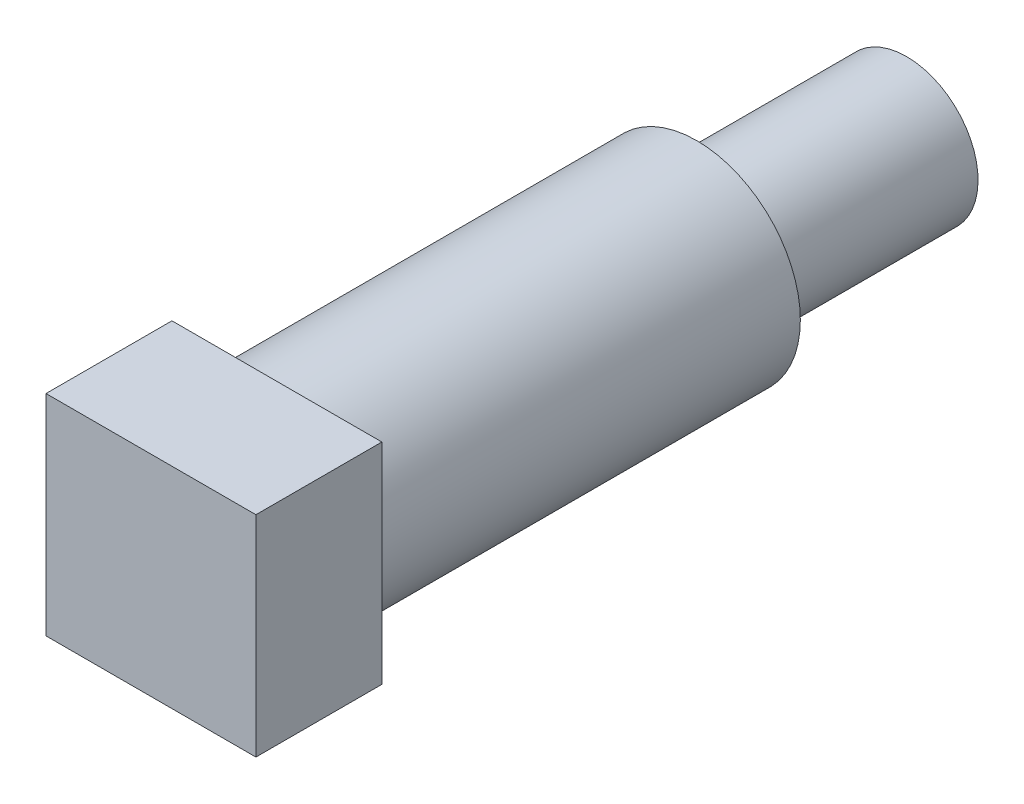
SolidWorks part; units mm, degrees
material "Alloy Steel (SS)"
ref_plane "Front Plane" through (0, 0, 0) normal (0, 0, 1) x (1, 0, 0)
ref_plane "Top Plane" through (0, 0, 0) normal (0, 1, 0) x (1, 0, 0)
ref_plane "Right Plane" through (0, 0, 0) normal (1, 0, 0) x (0, 0, -1)
sketch "Sketch1" plane through (0, 0, 0) normal (1, 0, 0) x (0, 0, -1)
  line L0 (4.8921, 0) -> (44.3738, 0)
  line L1 (0, 3.194) -> (0, 4.064)
  line L2 (6.2738, 3.3115) -> (6.2738, 4.445)
  line L3 (0.635, 4.699) -> (6.0198, 4.699)
  line L4 (-1000, 4.699) -> (49000, 4.699) construction
  line L5 (-1000, 0) -> (49000, 0) construction
  line L6 (44.3738, 0) -> (44.3738, 2.159)
  line L7 (0, -1000) -> (0, 49000) construction
  line L8 (6.2738, -1000) -> (6.2738, 49000) construction
  line L9 (44.3738, -1000) -> (44.3738, 49000) construction
  line L10 (0, 3.194) -> (0, 0)
  line L11 (0, 0) -> (4.8921, 0)
  line L15 (25.3238, 3.1236) -> (43.4092, 3.1236)
  line L17 (4.8921, 3.1236) -> (44.3738, 3.1236) construction
  line L18 (6.2738, 3.3115) -> (6.2738, 3.1337)
  line L19 (18.9738, 3.1337) -> (25.3238, 3.1236)
  line L20 (6.2738, 3.1337) -> (6.4516, 3.1337)
  line L21 (43.4092, 3.1236) -> (44.3738, 2.159)
  line L22 (6.4516, 3.1337) -> (18.9738, 3.1337)
  line L23 (4.8921, 3.1337) -> (44.3738, 3.1337) construction
  line L24 (6.0198, 4.699) -> (6.2738, 4.699)
  line L25 (6.2738, 4.699) -> (6.2738, 4.445)
  line L26 (0, 4.064) -> (0, 4.699)
  line L27 (0, 4.699) -> (0.635, 4.699)
  point P9 (0, 4.699)
  point P13 (6.2738, 4.699)
  dimension "D1" = 6.2738
  dimension "D2" = 4.699
  dimension "D10" = 3.1337
  dimension "D12" = 6.35
  dimension "D13" = 19.05
  dimension "D14" = 45
  dimension "D15" = 3.1236
  dimension "D16" = 0.9646
  dimension "D17" = 0.092
  dimension "D5" = 0.635
  dimension "D7" = 0.254
revolve "Revolve1" add sketch "Sketch1" angle 360 about L0
sketch "Sketch3" plane through (0, 0, -44.3738) normal (0, 0, -1) x (-1, 0, 0)
  circle A0 centre (0, 0) radius 3.1337
  circle A1 centre (0, 0) radius 2.159 construction
  dimension "D1" = 6.2674
curve "Helix/Spiral1" pitch 1.27 height 38.1 turns 30
sketch "Sketch4" plane through (0, 0, 0) normal (1, 0, 0) x (0, 0, -1)
  line L0 (44.3738, 3.1236) -> (44.5325, 3.1236) construction
  line L1 (45.207, 2.3669) -> (45.0882, 2.1612) construction
  line L2 (44.3738, 3.1236) -> (44.4532, 3.261) construction
  line L3 (44.9294, 2.4362) -> (45.2469, 2.4362) construction
  line L4 (44.4532, 3.261) -> (44.5325, 3.1236) construction
  line L5 (45.0882, 2.1612) -> (44.9694, 2.3669) construction
  line L6 (44.5118, 3.1594) -> (44.9694, 2.3669)
  line L7 (45.207, 2.3669) -> (45.6645, 3.1594)
  line L8 (44.5118, 3.1594) -> (45.6645, 3.1594)
  line L9 (44.3738, 2.159) -> (44.3738, -2.159) construction
  arc A0 (44.9694, 2.3669) -> (45.207, 2.3669) centre (45.0882, 2.4355) ccw
  dimension "D9" = 0.1372
  dimension "D2" = 1.0999
  dimension "D5" = 0.275
  dimension "D6" = 1.1527
  dimension "D7" = 0.7144
  dimension "D10" = 0.7233
  dimension "D11" = 0.0692
  dimension "D13" = 0.1587
  dimension "D3" = 0.1375
  dimension "D4" = 0.3175
  dimension "D8" = 60
sweep "Cut-Sweep1" [suppressed] cut profiles "Sketch4" path "Helix/Spiral1"
sketch "Sketch5" [suppressed] plane through (0, 0, 0) normal (1, 0, 0) x (0, 0, -1)
  line L3 (6.4267, 3.1337) -> (6.8694, 2.3669)
  line L4 (7.107, 2.3669) -> (7.5497, 3.1337)
  line L5 (7.5497, 3.1337) -> (6.4267, 3.1337)
  line L6 (6.4267, 3.1337) -> (6.8694, 2.3669)
  line L7 (7.107, 2.3669) -> (7.5497, 3.1337)
  line L8 (7.5497, 3.1337) -> (6.4267, 3.1337)
  arc A1 (6.8694, 2.3669) -> (7.107, 2.3669) centre (6.9882, 2.4355) ccw
  arc A2 (6.8694, 2.3669) -> (7.107, 2.3669) centre (6.9882, 2.4355) ccw
  dimension "D1" = 0
extrude "Cut-Extrude2" [suppressed] cut sketch "Sketch5" against normal through all
sketch "Sketch6" plane through (0, 0, -44.3738) normal (0, 0, -1) x (-1, 0, 0)
  circle A0 centre (0, 0) radius 3.6875
extrude "Cut-Extrude3" cut sketch "Sketch6" against normal blind 29.1338
sketch "Sketch7" plane through (0, 0, -15.24) normal (0, 0, -1) x (-1, 0, 0)
  circle A0 centre (0, 0) radius 3.1337
  dimension "D1" = 6.2675
extrude "Boss-Extrude1" add sketch "Sketch7" along normal blind 3.81 contours A0
sketch "Sketch8" plane through (0, 0, -19.05) normal (0, 0, -1) x (-1, 0, 0)
  circle A0 centre (0, 0) radius 2.159
extrude "Boss-Extrude2" add sketch "Sketch8" along normal blind 6.35
sketch "Sketch9" plane through (0, 0, 0) normal (0, 0, 1) x (1, 0, 0)
  circle A0 centre (0, 0) radius 4.699
extrude "Cut-Extrude4" cut sketch "Sketch9" against normal blind 6.35
sketch "Sketch10" plane through (0, 0, -6.35) normal (0, 0, 1) x (1, 0, 0)
  line L1 (-3.175, 3.175) -> (3.175, 3.175)
  line L2 (-3.175, 3.175) -> (-3.175, -3.175)
  line L3 (-3.175, -3.175) -> (3.175, -3.175)
  line L4 (3.175, 3.175) -> (3.175, -3.175)
  line L5 (-3.175, 3.175) -> (3.175, -3.175) construction
  line L6 (-3.175, -3.175) -> (3.175, 3.175) construction
  point P0 (0, 0)
  dimension "D1" = 6.35
  dimension "D2" = 6.35
extrude "Boss-Extrude3" add sketch "Sketch10" along normal blind 3.81
sketch "Stock Rod Diameter" [suppressed] plane through (0, 0, -2.54) normal (0, 0, 1) x (1, 0, 0)
  circle A0 centre (0, 0) radius 4.7625
  dimension "D1" = 9.525
equation "\"P\"= .05in"
equation "\"H\"= \"P\" * cos ( 30deg )"
equation "\"D13@Sketch4\" = .125 * \"P\""
equation "\"D2@Sketch4\" = \"H\""
equation "\"D3@Sketch4\" = .125 * \"H\""
equation "\"D5@Sketch4\" = .25 * \"H\""
equation "\"D4@Sketch4\" = .25 * \"P\""
equation "\"D9@Sketch4\" = .108 * \"P\""
